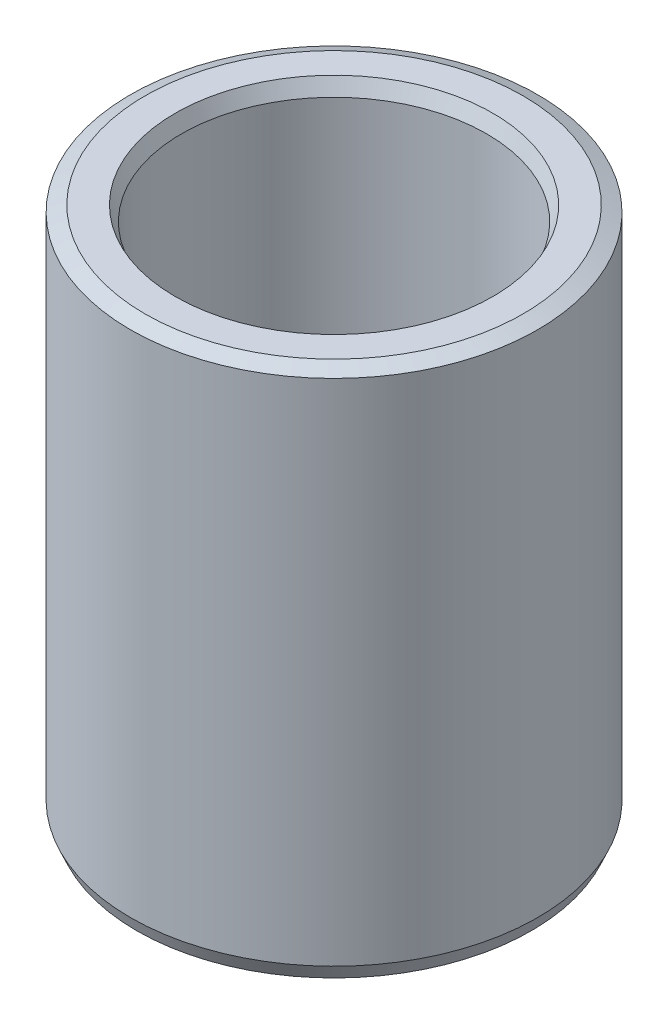
SolidWorks part; units mm, degrees
ref_plane "Front Plane" through (0, 0, 0) normal (0, 0, 1) x (1, 0, 0)
ref_plane "Top Plane" through (0, 0, 0) normal (0, 1, 0) x (1, 0, 0)
ref_plane "Right Plane" through (0, 0, 0) normal (1, 0, 0) x (0, 0, -1)
sketch "Sketch1" plane through (0, 0, 0) normal (0, 1, 0) x (1, 0, 0)
  circle A0 centre (0, 0) radius 35
  dimension "SLEEVE_OD" = 70
extrude "Boss-Extrude1" add sketch "Sketch1" along normal blind 91.1094
sketch "Sketch2" plane through (0, 0, 0) normal (0, 1, 0) x (1, 0, 0)
  circle A0 centre (0, 0) radius 26.2151
  dimension "BORE_D" = 52.4302
extrude "Cut-Extrude1" cut sketch "Sketch2" along normal through all
chamfer "Chamfer1" distance 1.0885 angle 66.608 4 edges at (0, 91.1094, 26.2151) (0, 0, 26.2151) (0, 0, 35) (0, 91.1094, 35) first distance on face at (0, 91.1094, 26.2151) first distance on face at (0, 0, 26.2151) first distance on face at (0, 91.1094, 35)
